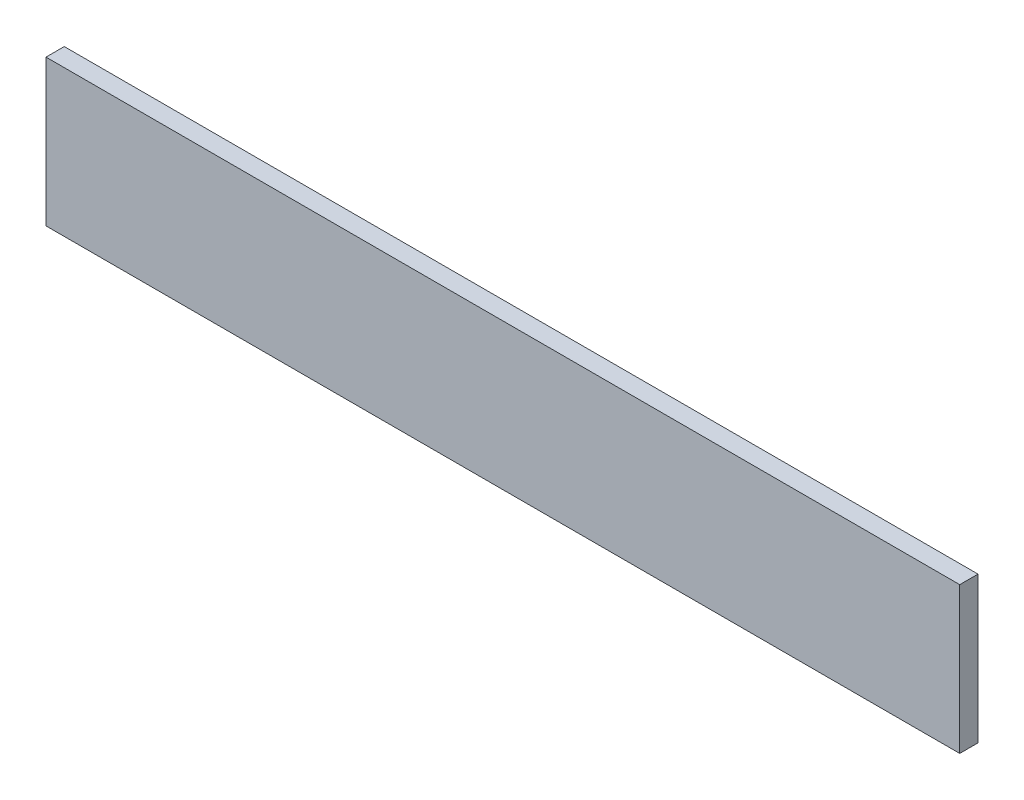
SolidWorks part; units mm, degrees
material "Pine"
ref_plane "Front Plane" through (0, 0, 0) normal (0, 0, 1) x (1, 0, 0)
ref_plane "Top Plane" through (0, 0, 0) normal (0, 1, 0) x (1, 0, 0)
ref_plane "Right Plane" through (0, 0, 0) normal (1, 0, 0) x (0, 0, -1)
sketch "Sketch1" plane through (0, 0, 0) normal (0, 0, 1) x (1, 0, 0)
  line L1 (-250, -40) -> (250, -40)
  line L2 (-250, -40) -> (-250, 40)
  line L3 (-250, 40) -> (250, 40)
  line L4 (250, -40) -> (250, 40)
  line L5 (-250, -40) -> (250, 40) construction
  line L6 (-250, 40) -> (250, -40) construction
  point P0 (0, 0)
  dimension "D1" = 500
  dimension "D2" = 80
extrude "Boss-Extrude1" add sketch "Sketch1" along normal blind 10
sketch "Sketch3" plane through (0, 0, 10) normal (0, 0, 1) x (1, 0, 0)
  line L0 (-250, 0) -> (250, 0) construction
  line L1 (-250, 40) -> (-250, -40) construction
  line L2 (250, -40) -> (250, 40) construction
  line L3 (0, 40) -> (0, -40) construction
  line L4 (250, 40) -> (-250, 40) construction
  line L5 (-250, -40) -> (250, -40) construction
  circle A0 centre (0, 0) radius 4
  circle A1 centre (-70, 0) radius 4
  circle A2 centre (-140, 0) radius 4
  circle A3 centre (-210, 0) radius 4
  circle A4 centre (210, 0) radius 4
  circle A5 centre (140, 0) radius 4
  circle A6 centre (70, 0) radius 4
  dimension "D1" = 8
  dimension "D2" = 8
  dimension "D3" = 8
  dimension "D4" = 8
  dimension "D5" = 70
  dimension "D6" = 140
  dimension "D7" = 210
